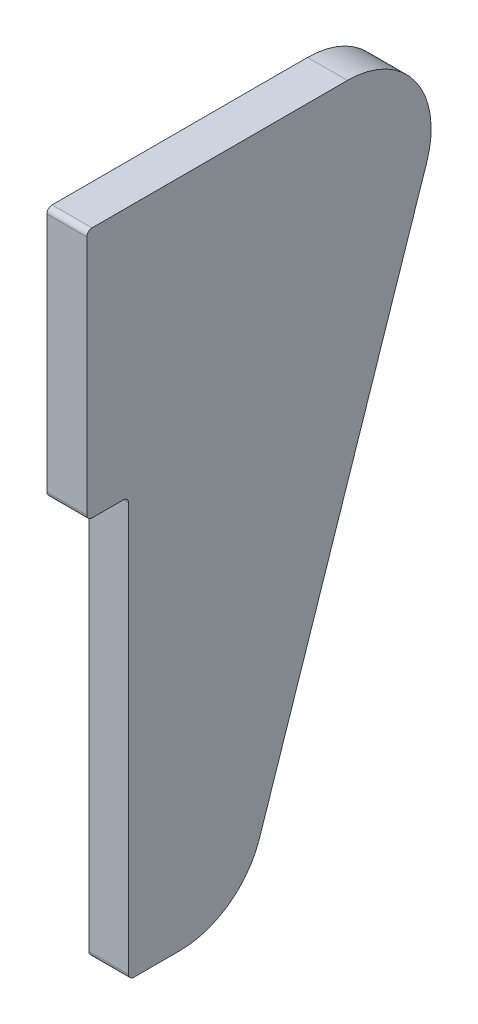
SolidWorks part; units mm, degrees
material "Plain Carbon Steel"
ref_plane "Front" through (0, 0, 0) normal (0, 0, 1) x (1, 0, 0)
ref_plane "Top" through (0, 0, 0) normal (0, 1, 0) x (1, 0, 0)
ref_plane "Right" through (0, 0, 0) normal (1, 0, 0) x (0, 0, -1)
sketch "Sketch1" plane through (0, 0, 0) normal (1, 0, 0) x (0, 0, -1)
  line L0 (0, -19.05) -> (0, -50.8)
  line L1 (8.4667, -50.8) -> (25.4, 0)
  line L2 (25.4, 0) -> (0, 0)
  line L3 (0, 0) -> (0, -19.05) construction
  line L4 (0, 0) -> (-3.175, 0)
  line L6 (0, -19.05) -> (-3.175, -19.05)
  line L7 (-3.175, 0) -> (-3.175, -19.05)
  line L8 (0, 0) -> (-3.175, -19.05) construction
  line L9 (0, -19.05) -> (-3.175, 0) construction
  line L10 (0, 0) -> (0, -19.05) construction
  line L11 (0, -50.8) -> (8.4667, -50.8)
  line L12 (0, -76.2) -> (8.4667, -50.8) construction
  line L13 (0, -50.8) -> (0, -76.2) construction
  point P7 (-1.5875, -9.525)
  dimension "D1" = 19.05
  dimension "D2" = 3.175
  dimension "D3" = 76.2
  dimension "D4" = 25.4
  dimension "D5" = 50.8
base flange "Base-Flange1" sketch "Sketch1" thickness 3.0226 reverse thickness direction no parameters "D1"=3.7592
ref_plane "Midplane" through (-1.5113, 0, 0) normal (1, 0, 0) x (0, 0, -1)
fillet "Fillet1" radius 6.35
fillet "Fillet2" radius 0.3969
sketch "Bend-Lines1" [suppressed] plane through (0, 0, 0) normal (0, 1, 0) x (1, 0, 0)
sketch "Bounding-Box1" [suppressed] plane through (0, 0, 0) normal (0, 1, 0) x (1, 0, 0)
sheet metal parameters "Sheet-Metal28" thickness 3.0226 parameters "D1"=3.7592
flat pattern "Flat-Pattern28" [suppressed]
sketch "Bend-Lines2" plane through (0, 0, 0) normal (0, 1, 0) x (1, 0, 0)
sketch3d "Bounding-Box2" [suppressed]
  line L0 (22.9397, 0, 0) -> (22.9397, -50.8, 0) construction
  line L1 (-3.175, 0, 0) -> (-3.175, -50.8, 0) construction
  line L2 (22.9397, 0, 0) -> (-3.175, 0, 0) construction
  line L3 (22.9397, -50.8, 0) -> (-3.175, -50.8, 0) construction
equation "\"Total Cutting Length\"= \"Cutting Length-Outer\" + \"Cutting Length-Inner\""
equation "\"Amount in ft^2\"= \"Bounding Box Area-Blank\" / 144"
